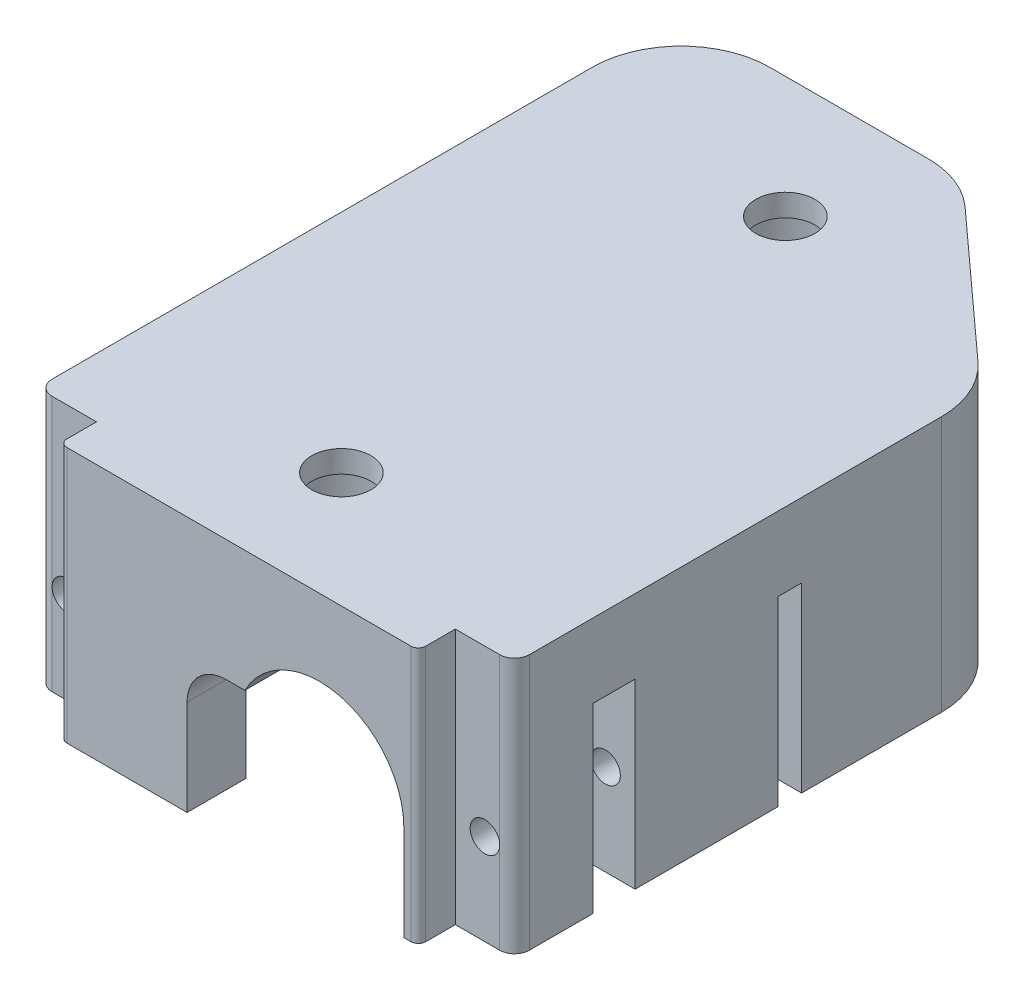
SolidWorks part; units mm, degrees
other "Marquage1"
sketch "Esquisse21" plane through (32.25, -12.3, -10.1) normal (0.0501, -0.9946, -0.0909) x (0.2438, -0.076, 0.9668)
sketch "Esquisse23" plane through (32.25, -12.3, -14.1) normal (0.0501, -0.9946, -0.0909) x (0.2438, -0.076, 0.9668)
ref_plane "Plan de face" through (0, 0, 0) normal (0, 0, 1) x (1, 0, 0)
ref_plane "Plan de dessus" through (0, 0, 0) normal (0, 1, 0) x (1, 0, 0)
ref_plane "Plan de droite" through (0, 0, 0) normal (1, 0, 0) x (0, 0, -1)
sketch "Esquisse1" plane through (0, 0, 0) normal (0, 0, 1) x (1, 0, 0)
  line L1 (0, 0) -> (32.25, 0)
  line L2 (0, 0) -> (0, -12.3)
  line L3 (0, -12.3) -> (32.25, -12.3)
  line L4 (32.25, 0) -> (32.25, -12.3)
  dimension "D1" = 32.25
  dimension "D2" = 12.3
extrude "Boss.-Extru.1" add sketch "Esquisse1" along normal blind 5
sketch "Esquisse2" plane through (0, 0, 5) normal (0, 0, 1) x (1, 0, 0)
  line L0 (0, -12.3) -> (32.25, -12.3) construction
  line L1 (0, 0) -> (4.7, 0)
  line L2 (0, 0) -> (0, -12.3)
  line L3 (0, -12.3) -> (4.7, -12.3)
  line L4 (4.7, 0) -> (4.7, -12.3)
  line L6 (32.25, 0) -> (27.55, 0)
  line L7 (32.25, 0) -> (32.25, -12.3)
  line L8 (32.25, -12.3) -> (27.55, -12.3)
  line L9 (27.55, 0) -> (27.55, -12.3)
  dimension "D1" = 4.7
  dimension "D2" = 4.7
extrude "Boss.-Extru.2" add sketch "Esquisse2" along normal blind 16.25
sketch "Esquisse5" plane through (0, 0, 0) normal (0, 0, -1) x (-1, 0, 0)
  line L1 (-32.25, 0) -> (0, 0)
  line L2 (-32.25, 0) -> (-32.25, 5)
  line L3 (-32.25, 5) -> (0, 5)
  line L4 (0, 0) -> (0, 5)
  dimension "D1" = 5
  dimension "D2" = 32.25
extrude "Boss.-Extru.4" add sketch "Esquisse5" against normal blind 27.9
sketch "Esquisse6" plane through (0, 0, 0) normal (0, -1, 0) x (1, 0, 0)
  line L1 (32.25, 27.9) -> (27.55, 27.9)
  line L2 (32.25, 27.9) -> (32.25, 24.1)
  line L3 (32.25, 24.1) -> (27.55, 24.1)
  line L4 (27.55, 27.9) -> (27.55, 24.1)
  line L5 (0, 27.9) -> (4.7, 27.9)
  line L6 (0, 27.9) -> (0, 24.1)
  line L7 (0, 24.1) -> (4.7, 24.1)
  line L8 (4.7, 27.9) -> (4.7, 24.1)
  dimension "D1" = 4.7
  dimension "D2" = 4.7
  dimension "D3" = 3.8
  dimension "D4" = 3.8
extrude "Boss.-Extru.5" add sketch "Esquisse6" along normal up to vertex (12.3 mm away) up to point (32.25, -12.3, 21.25)
sketch "Esquisse7" plane through (0, 0, 27.9) normal (0, 0, 1) x (1, 0, 0)
  line L0 (4.7, -12.3) -> (0, -12.3) construction
  line L1 (32.25, 5) -> (0, 5)
  line L2 (32.25, 5) -> (32.25, -12.3)
  line L3 (32.25, -12.3) -> (0, -12.3)
  line L4 (0, 5) -> (0, -12.3)
  line L5 (0, -12.3) -> (0, 5) construction
extrude "Boss.-Extru.6" add sketch "Esquisse7" along normal blind 4
sketch "Esquisse8" plane through (0, 0, 31.9) normal (0, 0, 1) x (1, 0, 0)
  line L0 (32.25, -12.3) -> (32.25, 5) construction
  line L1 (15.27, -5.85) -> (21.57, -5.85) construction
  line L2 (32.25, 5) -> (0, 5) construction
  line L3 (0, -12.3) -> (32.25, -12.3) construction
  line L4 (12.62, -5.85) -> (12.62, -12.3)
  line L5 (15.27, -3.2) -> (16.5235, -3.2)
  line L9 (27.27, -5.85) -> (27.27, -12.3)
  line L10 (27.27, -12.3) -> (12.62, -12.3)
  arc A0 (27.27, -5.85) -> (16.5235, -3.2) centre (21.57, -5.85) ccw
  arc A1 (15.27, -3.2) -> (12.62, -5.85) centre (15.27, -5.85) ccw
  dimension "D3" = 11.4
  dimension "D4" = 5.3
  dimension "D1" = 10.68
  dimension "D2" = 10.85
  dimension "D5" = 6.3
extrude "Enlèv. mat.-Extru.2" cut sketch "Esquisse8" against normal blind 4.3
sketch "Esquisse9" plane through (0, -12.3, 0) normal (0, -1, 0) x (1, 0, 0)
  line L0 (27.55, 21.25) -> (27.55, 5) construction
  line L1 (27.55, 10) -> (32.25, 10)
  line L2 (27.55, 10) -> (27.55, 11.6)
  line L3 (27.55, 11.6) -> (32.25, 11.6)
  line L4 (32.25, 10) -> (32.25, 11.6)
  line L5 (32.25, 21.25) -> (32.25, 0) construction
  dimension "D1" = 5
  dimension "D2" = 1.6
extrude "Enlèv. mat.-Extru.3" cut sketch "Esquisse9" against normal up to vertex (12.3 mm away) up to point (32.25, 0, 24.1)
sketch "Esquisse10" plane through (0, 0, 31.9) normal (0, 0, 1) x (1, 0, 0)
  line L0 (27.27, -12.3) -> (32.25, -12.3) construction
  line L2 (16.125, 5) -> (16.125, -12.3) construction
  line L3 (32.25, 5) -> (0, 5) construction
  line L4 (4.7, -12.3) -> (27.55, -12.3) construction
  circle A1 centre (30.25, -6.15) radius 1
  circle A3 centre (2, -6.15) radius 1
  dimension "D3" = 2
  dimension "D1" = 28.25
  dimension "D2" = 6.15
extrude "Enlèv. mat.-Extru.4" cut sketch "Esquisse10" against normal up to vertex (20.3 mm away) up to point (32.25, 0, 11.6)
sketch "Esquisse16" plane through (0, 0, 0) normal (0, 0, -1) x (-1, 0, 0)
  line L1 (0, 5) -> (-32.25, 5)
  line L2 (0, 5) -> (0, -12.3)
  line L3 (0, -12.3) -> (-32.25, -12.3)
  line L4 (-32.25, 5) -> (-32.25, -12.3)
extrude "Boss.-Extru.8" add sketch "Esquisse16" along normal blind 14.1
sketch "Esquisse18" plane through (0, 5, 0) normal (0, 1, 0) x (1, 0, 0)
  line L0 (32.25, -31.9) -> (0, -31.9) construction
  line L1 (32.25, -31.9) -> (32.25, 14.1) construction
  line L3 (15.25, -24.1) -> (15.25, 5.9) construction
  circle A0 centre (15.25, -24.1) radius 2
  circle A1 centre (15.25, 5.9) radius 2
  dimension "D2" = 4
  dimension "D5" = 4
  dimension "D1" = 7.8
  dimension "D3" = 17
  dimension "D4" = 30
extrude "Enlèv. mat.-Extru.8" cut sketch "Esquisse18" against normal up to vertex (17.3 mm away) up to point (32.25, -12.3, 11.6)
fillet "Congé4" radius 6 1 edges at (0, -3.65, -14.1)
sketch "Esquisse19" plane through (0, -12.3, 0) normal (0, -1, 0) x (1, 0, 0)
  circle A0 centre (15.25, -5.9) radius 3.8
  circle A1 centre (15.25, 24.1) radius 3.8
  dimension "D1" = 7.6
extrude "Enlèv. mat.-Extru.9" cut sketch "Esquisse19" against normal blind 15.8
sketch "Esquisse20" plane through (0, 0, 31.9) normal (0, 0, 1) x (1, 0, 0)
  line L0 (0, -12.3) -> (12.62, -12.3) construction
  line L1 (0, 5) -> (4, 5)
  line L2 (0, 5) -> (0, -12.3)
  line L3 (0, -12.3) -> (4, -12.3)
  line L4 (4, 5) -> (4, -12.3)
  line L5 (27.27, -12.3) -> (32.25, -12.3) construction
  line L6 (32.25, 5) -> (28.25, 5)
  line L7 (32.25, 5) -> (32.25, -12.3)
  line L8 (32.25, -12.3) -> (28.25, -12.3)
  line L9 (28.25, 5) -> (28.25, -12.3)
  dimension "D1" = 4
  dimension "D2" = 4
extrude "Enlèv. mat.-Extru.10" cut sketch "Esquisse20" against normal blind 2.5
sketch "Esquisse22" plane through (0, -12.3, 0) normal (0, -1, 0) x (1, 0, 0)
  line L0 (19.0381, -14.1) -> (32.25, -2.1)
  line L5 (32.25, -14.1) -> (6, -14.1) construction
  line L6 (32.25, 10) -> (32.25, -14.1) construction
  line L7 (32.25, -2.1) -> (32.25, -14.1)
  line L8 (32.25, -14.1) -> (19.0381, -14.1)
  line L9 (19.0381, -5.6) -> (19.0381, -14.1) construction
  line L10 (15.25, -2.1) -> (32.25, -2.1) construction
  circle A1 centre (15.25, -5.9) radius 3.8 construction
  circle A2 centre (15.25, -5.9) radius 3.8 construction
  dimension "D1" = 17
  dimension "D2" = 8.5
extrude "Enlèv. mat.-Extru.11" cut sketch "Esquisse22" against normal up to vertex (17.3 mm away) up to point (32.25, 5, -14.1)
fillet "Congé5" radius 6 1 edges at (19.0381, -3.65, -14.1)
fillet "Congé6" radius 6 1 edges at (32.25, -3.65, -2.1)
fillet "Congé7" radius 1 1 edges at (32.25, -3.65, 29.4)
fillet "Congé8" radius 1 1 edges at (0, -3.65, 29.4)
fillet "Congé9" radius 0.5 1 edges at (28.25, -3.65, 31.9)
fillet "Congé10" radius 0.5 1 edges at (4, -3.65, 31.9)
fillet "Congé11" radius 0.5 6 edges at (27.55, -6.15, 10) (27.55, -6.15, 11.6) (4.7, -6.15, 21.25) (4.7, -6.15, 24.1) (27.55, -6.15, 21.25) (27.55, -6.15, 24.1)
